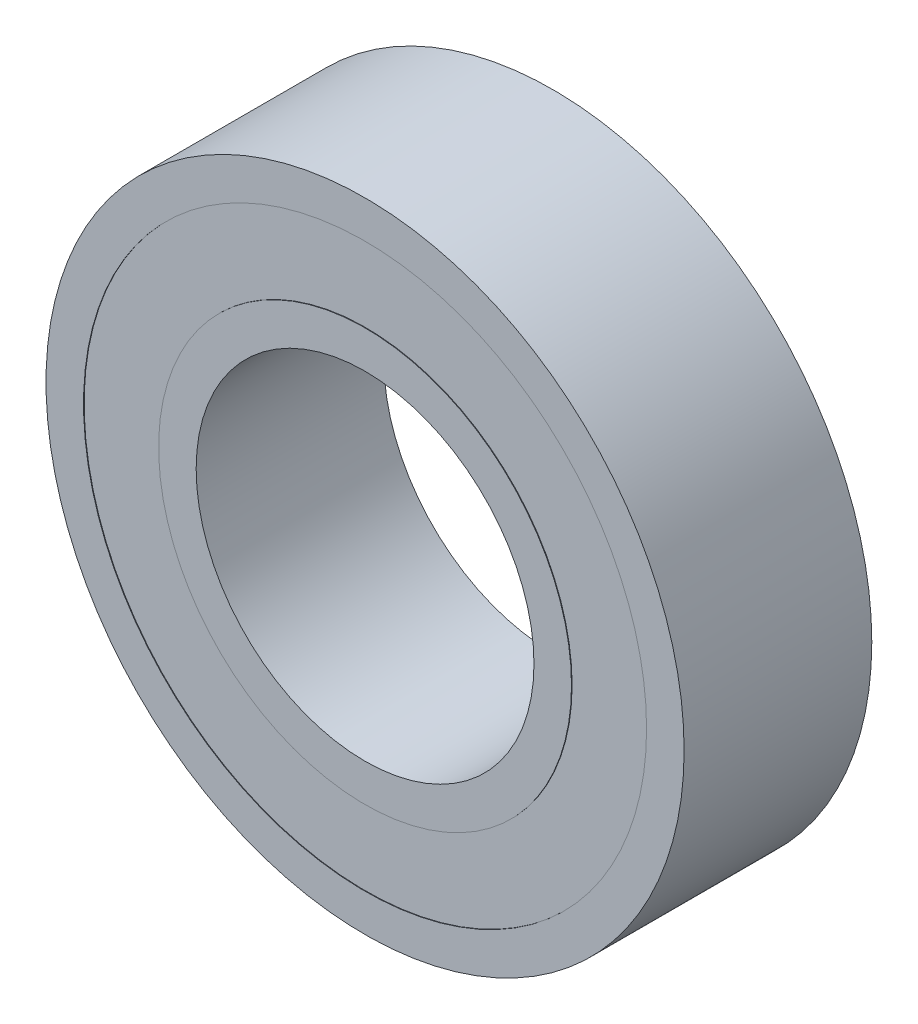
SolidWorks part; units mm, degrees
material "Chrome Stainless Steel"
ref_plane "Front Plane" through (0, 0, 0) normal (0, 0, 1) x (1, 0, 0)
ref_plane "Top Plane" through (0, 0, 0) normal (0, 1, 0) x (1, 0, 0)
ref_plane "Right Plane" through (0, 0, 0) normal (1, 0, 0) x (0, 0, -1)
sketch "Sketch1" plane through (0, 0, 0) normal (0, 0, 1) x (1, 0, 0)
  circle A0 centre (0, 0) radius 4.5
  circle A1 centre (0, 0) radius 5.5
  circle A2 centre (0, 0) radius 8.5
  circle A3 centre (0, 0) radius 7.5
  dimension "D1" = 17
  dimension "D2" = 9
  dimension "D3" = 11
  dimension "D4" = 15
extrude "Boss-Extrude1" add sketch "Sketch1" along normal blind 2.5 and the other way blind 2.5 contours A2 A3 | A1 A0 region at (-5.3444, 0, 0) region at (-8.2596, 0, 0)
extrude "Boss-Extrude2" add sketch "Sketch1<3>" along normal blind 2.4844 and the other way blind 2.4844 contours A3 A1 region at (-7.2879, 0, 0)
sketch "Sketch1<3>" plane through (0, 0, 0) normal (0, 0, 1) x (1, 0, 0) same geometry as "Sketch1"
equation "\"D1@Boss-Extrude2\"=2.5mm-1/64"
equation "\"D2@Boss-Extrude2\"=2.5mm-1/64"
